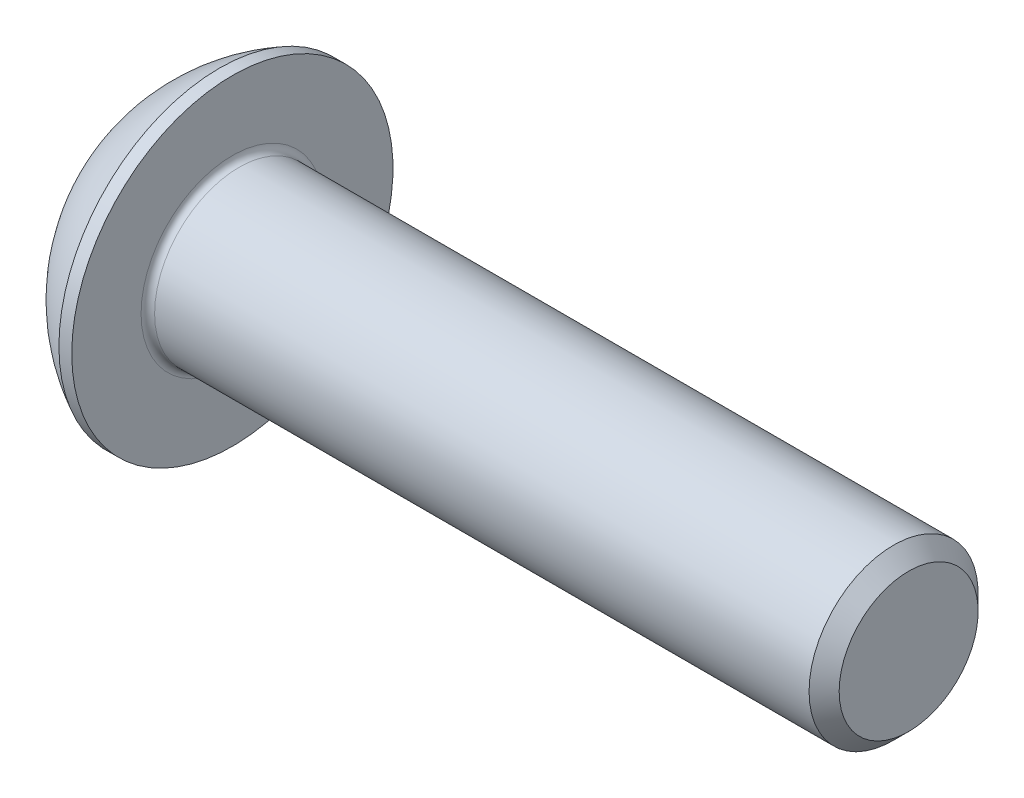
SolidWorks part; units mm, degrees
ref_plane "Plane1" through (0, 0, 0) normal (0, 0, 1) x (1, 0, 0)
ref_plane "Plane2" through (0, 0, 0) normal (0, 1, 0) x (1, 0, 0)
ref_plane "Plane3" through (0, 0, 0) normal (1, 0, 0) x (0, 0, -1)
sketch "BodySke" plane through (0, 0, 0) normal (0, 0, 1) x (1, 0, 0)
  line L0 (22.75, 0) -> (22.75, 2.055)
  line L1 (22.305, 2.5) -> (2.75, 2.5)
  line L2 (2.75, 2.5) -> (2.75, 4.75)
  line L3 (2.75, 4.75) -> (2.37, 4.75)
  line L4 (0, 0) -> (101.6, 0) construction
  line L5 (2.75, -4.75) -> (2.37, -4.75) construction
  line L6 (55.6768, -2.5) -> (2.75, -2.5) construction
  line L7 (22.75, 0) -> (0, 0)
  line L8 (0, 2.375) -> (0, -2.375) construction
  line L9 (0, 0) -> (0, 2.375)
  line L10 (22.75, 2.055) -> (22.305, 2.5)
  line L11 (22.75, -2.055) -> (22.305, -2.5) construction
  line L12 (3.55, 9.525) -> (3.55, -2.5) construction
  line L13 (6.75, 9.525) -> (6.75, -2.5) construction
  arc A1 (0, 2.375) -> (2.37, 4.75) centre (4.755, 0) cw
  dimension "D1" = 4.75
  dimension "Diameter" = 5
  dimension "Advance" = 0.8
revolve "BaseBody" add sketch "BodySke" angle 360 about L4
cosmetic thread "ThreadCosmetic" [suppressed] parameters "Thread_length"=16, "Thread_minor"=4.11
fillet "Fillet1" radius 0.2 1 edges at (2.75, 0, 2.5)
sketch "Sketch2" plane through (0, 0, 0) normal (0, 0, 1) x (1, 0, 0)
  line L0 (0, 1.5) -> (1.56, 1.5)
  line L1 (1.56, 1.5) -> (2.426, 0)
  line L3 (2.426, 0) -> (0, 0)
  line L4 (0, 0) -> (0, 1.5)
  line L5 (0, -1.5) -> (1.56, -1.5) construction
  line L6 (0, 0) -> (47.625, 0) construction
  dimension "D2" = 60
  dimension "PreBroach_depth" = 1.56
  dimension "PreBroach_dia" = 3
revolve "PreBroach" cut sketch "Sketch2" angle 360 about L6
sketch "Sketch3" plane through (0, 0, 0) normal (1, 0, 0) x (0, 0, -1)
  line L0 (-1.5, -0.866) -> (-1.5, 0.866)
  line L1 (-1.5, 0.866) -> (0, 1.7321)
  line L2 (0, 1.7321) -> (1.5, 0.866)
  line L3 (1.5, 0.866) -> (1.5, -0.866)
  line L4 (1.5, -0.866) -> (0, -1.7321)
  line L5 (0, -1.7321) -> (-1.5, -0.866)
  dimension "Hex_size" = 3
  dimension "D3" = 3
  dimension "D1" = 1.5
  dimension "D2" = 1.5
extrude "Hex" cut sketch "Sketch3" along normal blind 1.56
sketch "ThdSchSke" plane through (0, 0, 0) normal (0, 0, 1) x (1, 0, 0)
  line L0 (6.75, -2.055) -> (6.4384, -2.5)
  line L1 (6.75, -2.055) -> (7.0616, -2.5)
  line L2 (7.0616, -2.5) -> (7.0616, -3.125)
  line L3 (-3.175, 0) -> (5.1513, 0) construction
  line L5 (7.0616, -3.125) -> (6.4384, -3.125)
  line L6 (6.4384, -3.125) -> (6.4384, -2.5)
  dimension "Thread_minor" = 4.11
  dimension "Diameter" = 5
revolve "ThreadSchematic" [suppressed] cut sketch "ThdSchSke" angle 360 about L3
pattern_linear "ThdSchPat" [suppressed]
equation "\"D1@BodySke\" = \"Head_dia@BodySke\" * .5"
equation "\"Thread_minor@ThreadCosmetic\" = \"Minor_dia@BodySke\""
equation "\"D1@Sketch3\" = \"Hex_size@Sketch3\" / 2"
equation "\"D2@Sketch3\" = \"D1@Sketch3\""
equation "\"D3@Sketch3\" = \"Hex_size@Sketch3\""
equation "\"Thread_length@ThreadCosmetic\" = ((sgn( (\"Length@BodySke\" - \"Advance@BodySke\" * 2.0) - \"Thread_nom@BodySke\" )-1)*( (\"Length@BodySke\" - \"Advance@BodySke\" * 2.0) - \"Thread_nom@BodySke\" ))/-2+ \"Thread_nom@BodySke\""
equation "\"Thread_minor@ThdSchSke\" = \"Minor_dia@BodySke\""
equation "\"Diameter@ThdSchSke\" = \"Diameter@BodySke\""
equation "\"Overcut@ThdSchSke\" = \"Diameter@BodySke\" * 1.25"
equation "\"Start@ThdSchSke\" = \"Head_ht@BodySke\" + \"Length@BodySke\" - \"Thread_length@ThreadCosmetic\"  '---Non-countersunk---"
equation "\"Num_threads@ThdSchPat\" = int( \"Thread_length@ThreadCosmetic\" / \"Advance@BodySke\" + 0.999 )  + 1"
equation "\"Advance@ThdSchPat\" = \"Thread_length@ThreadCosmetic\" /  (\"Num_threads@ThdSchPat\" - 1) 'relax it"
equation "\"Num_threads@ThdSchPat\" = \"Num_threads@ThdSchPat\" - sgn( \"Num_threads@ThdSchPat\" - 1) '---chamfered tips only---"
